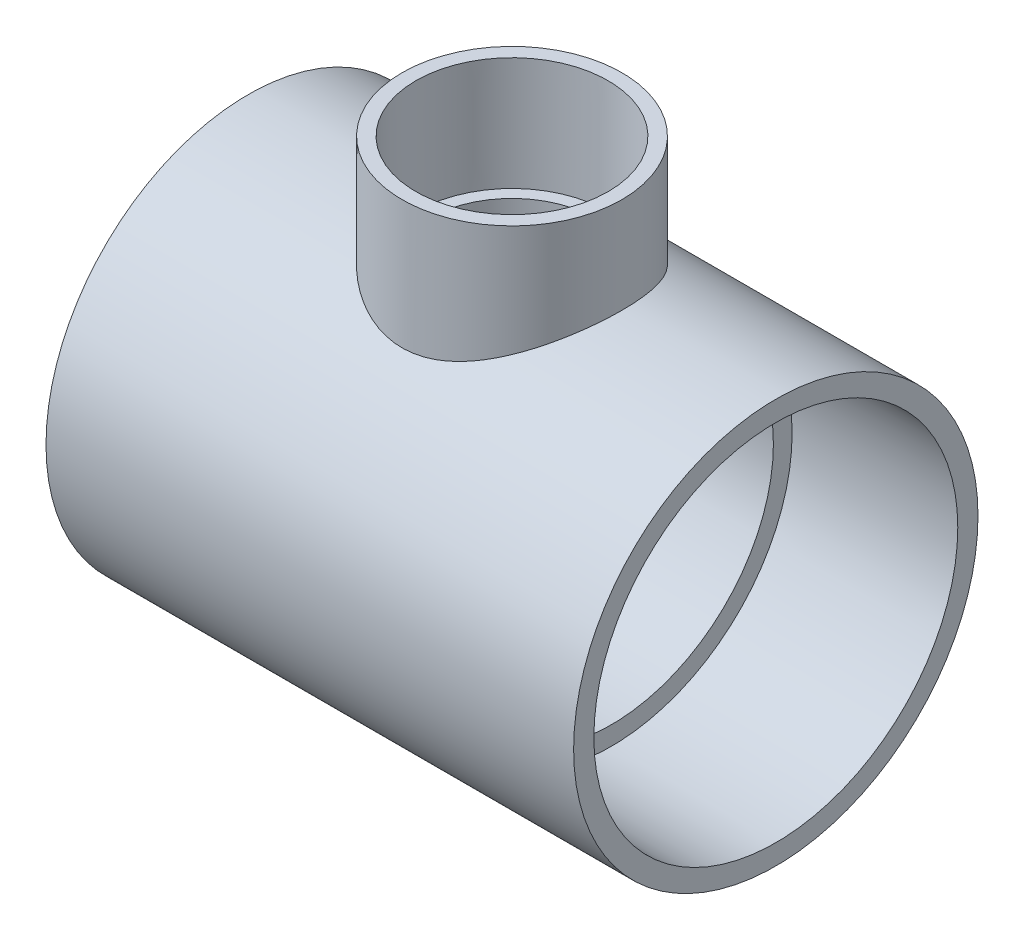
SolidWorks part; units mm, degrees
ref_plane "Front Plane" through (0, 0, 0) normal (0, 0, 1) x (1, 0, 0)
ref_plane "Top Plane" through (0, 0, 0) normal (0, 1, 0) x (1, 0, 0)
ref_plane "Right Plane" through (0, 0, 0) normal (1, 0, 0) x (0, 0, -1)
sketch "Sketch0" plane through (0, 0, 0) normal (0, 0, 1) x (1, 0, 0)
  line L0 (-83.185, 0) -> (0, 0) construction
  line L1 (0, 0) -> (0, 93.98) construction
  line L2 (-31.2928, 0) -> (0, 0) construction
  line L3 (0, 0) -> (0, 58.42) construction
  line L4 (-83.185, 63.754) -> (-83.185, -63.754) construction
  line L5 (-31.2928, 57.0357) -> (-83.185, 57.3786) construction
  line L6 (-31.2928, 57.0357) -> (-31.2928, -57.0357) construction
  line L7 (-31.2928, -57.0357) -> (-83.185, -57.3786) construction
  line L8 (-83.185, 57.3786) -> (-83.185, -57.3786) construction
  line L9 (-34.671, 93.98) -> (34.671, 93.98) construction
  line L10 (-30.3149, 93.98) -> (30.3149, 93.98) construction
  line L11 (30.3149, 93.98) -> (30.0863, 58.42) construction
  line L12 (30.0863, 58.42) -> (-30.0863, 58.42) construction
  line L13 (-30.0863, 58.42) -> (-30.3149, 93.98) construction
  line L14 (-31.2928, 51.1302) -> (-31.2928, -51.1302) construction
  line L15 (-83.185, 0) -> (-31.2928, 0) construction
  line L16 (0, 93.98) -> (0, 58.42) construction
  line L17 (0, 0) -> (31.2928, 0) construction
  line L18 (-26.2509, 58.42) -> (26.2509, 58.42) construction
  line L19 (31.2928, 0) -> (83.185, 0) construction
  dimension "D1" = 35.56
  dimension "H" = 83.185
  dimension "G" = 31.2928
  dimension "M" = 127.508
  dimension "OD A" = 114.7572
  dimension "OD B" = 114.0714
  dimension "ID" = 102.2604
  dimension "H3" = 93.98
  dimension "G3" = 58.42
  dimension "M3" = 69.342
  dimension "D2" = 51.8922
  dimension "OD A3" = 60.6298
  dimension "OD B3" = 60.1726
  dimension "ID3" = 52.5018
sketch "Sketch1" plane through (0, 0, 0) normal (0, 0, 1) x (1, 0, 0)
  line L0 (-83.185, 0) -> (0, 0) construction
  line L1 (-83.185, 0) -> (0, 0) construction
  line L2 (0, 0) -> (0, -63.754) construction
  line L3 (-83.185, -63.754) -> (-31.2928, -63.754)
  line L4 (-83.185, -63.754) -> (-83.185, -57.3786)
  line L5 (-83.185, -57.3786) -> (-31.2928, -57.0357)
  line L6 (-31.2928, -63.754) -> (-31.2928, -57.0357)
  line L7 (-31.2928, -63.754) -> (0, -63.754) construction
  line L8 (83.185, -57.3786) -> (31.2928, -57.0357)
  line L9 (83.185, -63.754) -> (83.185, -57.3786)
  line L10 (31.2928, -63.754) -> (31.2928, -57.0357)
  line L11 (83.185, -63.754) -> (31.2928, -63.754)
revolve "Revolve1" add sketch "Sketch1" angle 360 about L1
sketch "Sketch2" plane through (0, 0, 0) normal (0, 0, 1) x (1, 0, 0)
  line L0 (30.3149, 93.98) -> (30.0863, 58.42)
  line L1 (30.0863, 58.42) -> (34.671, 58.42)
  line L2 (34.671, 58.42) -> (34.671, 93.98)
  line L3 (34.671, 93.98) -> (30.3149, 93.98)
  line L4 (0, 0) -> (0, 93.98) construction
  line L5 (0, 0) -> (0, 93.98) construction
revolve "Revolve2" add sketch "Sketch2" angle 360 about L5
sketch "Sketch3" plane through (-31.2928, 0, 0) normal (1, 0, 0) x (0, 0, -1)
  circle A0 centre (0, 0) radius 51.1302
  circle A1 centre (0, 0) radius 63.754
sketch "Sketch4" plane through (-31.2928, 0, 0) normal (1, 0, 0) x (0, 0, -1)
  circle A0 centre (0, 0) radius 63.754 construction
  circle A1 centre (0, 0) radius 63.754
extrude "Boss-Extrude1" add sketch "Sketch4" along normal up to vertex (62.5856 mm away) up to point (31.2928, 0, 0)
sketch "Sketch5" plane through (0, 58.42, 0) normal (0, -1, 0) x (1, 0, 0)
  circle A0 centre (0, 0) radius 34.671 construction
  circle A1 centre (0, 0) radius 34.671
extrude "Boss-Extrude2" add sketch "Sketch5" along normal up to vertex (58.42 mm away) up to point (0, 0, 0)
sketch "Sketch6" plane through (0, 0, 0) normal (0, 0, 1) x (1, 0, 0)
  line L0 (-83.185, -57.3786) -> (-31.2928, -57.0357)
  line L1 (-31.2928, -57.0357) -> (-31.2928, -51.1302)
  line L2 (-31.2928, -51.1302) -> (31.2928, -51.1302)
  line L3 (31.2928, -57.0357) -> (31.2928, 55.0475) construction
  line L4 (0, -51.1302) -> (0, 0) construction
  line L5 (31.2928, -57.0357) -> (31.2928, -51.1302)
  line L6 (83.185, -57.3786) -> (83.185, 57.3786) construction
  line L7 (83.185, -63.754) -> (83.185, 63.754) construction
  line L8 (83.185, -57.3786) -> (83.185, 0)
  line L9 (83.185, 0) -> (-83.185, 0)
  line L10 (-83.185, 0) -> (-83.185, -57.3786)
  line L11 (83.185, -57.3786) -> (31.2928, -57.0357)
revolve "Cut-Revolve1" cut sketch "Sketch6" angle 360 about L9
sketch "Sketch7" plane through (0, 0, 0) normal (0, 0, 1) x (1, 0, 0)
  line L0 (30.3149, 93.98) -> (30.0863, 58.42)
  line L1 (30.0863, 58.42) -> (26.2509, 58.42)
  line L2 (26.2509, 58.42) -> (26.2509, 0)
  line L3 (0, 0) -> (31.2928, 0) construction
  line L4 (26.2509, 0) -> (0, 0)
  line L5 (0, 0) -> (0, 93.98)
  line L6 (-34.671, 93.98) -> (34.671, 93.98) construction
  line L7 (0, 93.98) -> (30.3149, 93.98)
revolve "Cut-Revolve2" cut sketch "Sketch7" angle 360 about L5
other "CPoint2" parameters "Diameter"=50.8, "StubLength"=152.4
ref_axis "Axis2" through (0, 68.42, 0) along (0, -1, 0)
other "CPoint3" parameters "Diameter"=101.6, "StubLength"=152.4
ref_axis "Axis3" through (-41.2928, 0, 0) along (1, 0, 0)
other "CPoint4" parameters "Diameter"=101.6, "StubLength"=152.4
ref_axis "Axis4" through (41.2928, 0, 0) along (-1, 0, 0)
other "RPoint1"
